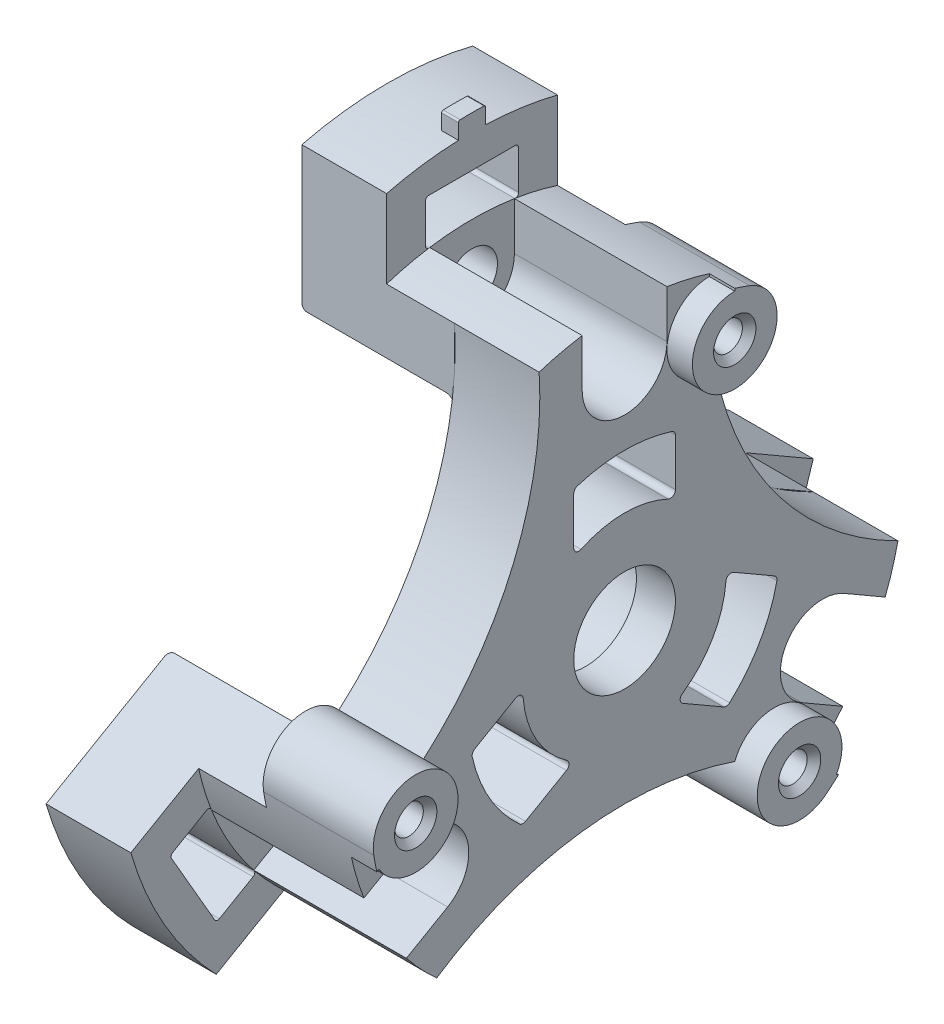
SolidWorks part; units mm, degrees
ref_plane "Front" through (0, 0, 0) normal (0, 0, 1) x (1, 0, 0)
ref_plane "Top" through (0, 0, 0) normal (0, 1, 0) x (1, 0, 0)
ref_plane "Right" through (0, 0, 0) normal (1, 0, 0) x (0, 0, -1)
sketch "草图1" plane through (0, 0, 0) normal (0, 0, 1) x (1, 0, 0)
  line L0 (-65.7429, 0) -> (89.5714, 0) construction
  line L1 (0, 67.1143) -> (0, -71.9143) construction
  line L2 (-7, 6) -> (-5, 6)
  line L3 (-5, 6) -> (-5, 16.5)
  line L4 (-5, 16.5) -> (0, 16.5)
  line L5 (0, 16.5) -> (0, 3)
  line L6 (-2.3, 3.975) -> (-7, 3.975)
  line L7 (-7, 3.975) -> (-7, 6)
  line L8 (-2.3, 3.975) -> (-2.3, 3)
  line L9 (-2.3, 3) -> (0, 3)
  dimension "D1" = 6
  dimension "D2" = 4.7
  dimension "D3" = 7.95
  dimension "D4" = 7
  dimension "D5" = 5
  dimension "D6" = 12
  dimension "D7" = 33
  dimension "D8" = 2.3
revolve "旋转1" add sketch "草图1" angle 360 about L0
sketch "草图2" plane through (-5, 0, 0) normal (-1, 0, 0) x (0, 0, 1)
  line L0 (-23.9515, 0) -> (26.381, 0) construction
  line L1 (0, 44.3891) -> (0, -20.5254) construction
  line L2 (0, 0) -> (-21.2641, -12.2768) construction
  line L3 (0, 0) -> (20.7932, -12.005) construction
  line L4 (0, 0) -> (-61.1055, 35.2793) construction
  line L5 (-5, 31.2128) -> (-5, 9) construction
  line L6 (5, 31.2128) -> (5, 9) construction
  circle A1 centre (-25, 14.4338) radius 20
  point P7 (0, 9)
  point P9 (-7.6795, 4.4338)
  dimension "D6" = 40
  dimension "D1" = 120
  dimension "D2" = 120
  dimension "D3" = 9
  dimension "D5" = 60
  dimension "D7" = 10
extrude "切除-拉伸1" cut sketch "草图2" against normal blind 10 contours A1
pattern_circular "阵列(圆周)1" count 3 over 360 about axis through (-7, 0, 0) along (-1, 0, 0) of "切除-拉伸1"
sketch "草图3" plane through (-5, 0, 0) normal (-1, 0, 0) x (0, 0, 1)
  line L0 (0, 18) -> (0, -12.9057) construction
  line L1 (-20.442, 0) -> (20.8303, 0) construction
  line L2 (-3, 8.4806) -> (-3, 5.6921)
  line L4 (3, 8.4806) -> (3, 5.6921)
  arc A0 (2.791, 8.7664) -> (-2.791, 8.7664) centre (0, 0) ccw
  circle A1 centre (0, 0) radius 6 construction
  arc A2 (2.5714, 5.421) -> (-2.5714, 5.421) centre (0, 0) ccw
  arc A3 (3, 5.6921) -> (2.5714, 5.421) centre (2.7, 5.6921) cw
  arc A4 (-2.5714, 5.421) -> (-3, 5.6921) centre (-2.7, 5.6921) cw
  arc A5 (3, 8.4806) -> (2.791, 8.7664) centre (2.7, 8.4806) ccw
  arc A6 (-2.791, 8.7664) -> (-3, 8.4806) centre (-2.7, 8.4806) ccw
  point P11 (3, 5.1962)
  point P16 (-3, 5.1962)
  point P19 (3, 8.6971)
  point P22 (-3, 8.6971)
  dimension "D1" = 9.2
  dimension "D3" = 0.3
  dimension "D2" = 6
extrude "切除-拉伸2" cut sketch "草图3" against normal blind 10
pattern_circular "阵列(圆周)2" count 3 over 360 about axis through (-2.3, 0, 0) along (-1, 0, 0) of "切除-拉伸2"
sketch "草图4" plane through (-5, 0, 0) normal (-1, 0, 0) x (0, 0, 1)
  line L0 (-16.7535, 0) -> (15.8993, 0) construction
  line L1 (0, 19.3876) -> (0, -16.6742) construction
  line L2 (-5.0408, 15.7111) -> (-5.0408, 11.9286)
  line L4 (5.0408, 11.9286) -> (5.0408, 15.7111)
  circle A0 centre (0, 0) radius 13.5 construction
  arc A1 (5.0408, 15.7111) -> (-5.0408, 15.7111) centre (0, 0) ccw construction
  arc A2 (5.0408, 15.7111) -> (-5.0408, 15.7111) centre (0, 0) ccw
  circle A3 centre (0, 13.5) radius 1.5
  arc A4 (-2.6744, 12.6708) -> (2.6744, 12.6708) centre (0, 13.5) ccw
  arc A5 (-2.6744, 12.6708) -> (-5.0408, 11.9286) centre (0, 0) ccw
  arc A6 (5.0408, 11.9286) -> (2.6744, 12.6708) centre (0, 0) ccw
  dimension "D1" = 27
  dimension "D2" = 3
  dimension "D4" = 5.6
  dimension "D5" = 25.9
extrude "凸台-拉伸1" add sketch "草图4" along normal blind 9
pattern_circular "阵列(圆周)3" count 3 over 360 about axis through (-65.7429, 0, 0) along (-1, 0, 0) of "凸台-拉伸1"
sketch "草图5" plane through (-14, 0, 0) normal (-1, 0, 0) x (0, 0, 1)
  line L0 (-16.1323, 0) -> (16.637, 0) construction
  line L1 (0, 17.8058) -> (0, -12.3621) construction
  line L3 (-2.8, 12.6437) -> (-2.8, 9.2908)
  line L4 (-2.8, 9.2908) -> (2.8, 9.2908)
  line L5 (2.8, 12.6437) -> (2.8, 9.2908)
  arc A2 (2.8, 12.6437) -> (-2.8, 12.6437) centre (0, 0) ccw
  point P10 (0, 9.2908)
  point P11 (0, 13.55)
  dimension "D1" = 5.6
  dimension "D2" = 25.9
extrude "切除-拉伸3" cut sketch "草图5" against normal blind 1.7 contours L4 L5 A2 L3
sketch "草图10" plane through (-5, 0, 0) normal (-1, 0, 0) x (0, 0, 1)
  point P1 (0, 0)
  dimension "D1" = 12.8775
pattern_circular "阵列(圆周)4" count 3 over 360 about axis through (-65.7429, 0, 0) along (-1, 0, 0) of "切除-拉伸3" reverse direction yes
sketch "草图6" plane through (0, 0, 0) normal (1, 0, 0) x (0, 0, -1)
  line L0 (-17.245, 0) -> (20.4566, 0) construction
  line L1 (0, 20.1005) -> (0, -14.3306) construction
  line L2 (-2.5, 16.3095) -> (-2.5, 13.5)
  line L3 (2.5, 16.3095) -> (2.5, 13.5)
  circle A0 centre (0, 0) radius 13.5 construction
  arc A1 (5.0408, 15.7111) -> (-5.0408, 15.7111) centre (0, 0) ccw construction
  arc A3 (2.5, 16.3095) -> (-2.5, 16.3095) centre (0, 0) ccw
  arc A4 (-2.5, 13.5) -> (2.5, 13.5) centre (0, 13.5) ccw
  dimension "D1" = 27
  dimension "D3" = 5
  dimension "D2" = 5
extrude "切除-拉伸4" cut sketch "草图6" against normal blind 9
pattern_circular "阵列(圆周)5" count 3 over 360 about axis through (-65.7429, 0, 0) along (-1, 0, 0) of "切除-拉伸4"
sketch "草图7" plane through (-5, 0, 0) normal (-1, 0, 0) x (0, 0, 1)
  line L0 (0, 19.1221) -> (0, -13.8647) construction
  line L1 (16.0973, 0) -> (-17.961, 0) construction
  line L2 (-5, 15.5767) -> (-5, 15.7242)
  arc A1 (-5.8929, 15.4118) -> (-5, 15.5767) centre (-5, 13.0767) ccw
  circle A5 centre (0, 0) radius 14 construction
  arc A6 (-2.5, 16.3095) -> (-5.0408, 15.7111) centre (0, 0) ccw construction
  arc A7 (-5, 15.7242) -> (-5.8929, 15.4118) centre (0, 0) ccw
  point P7 (-5, 13.0767)
  dimension "D1" = 28
  dimension "D3" = 5
  dimension "D2" = 5
extrude "凸台-拉伸2" add sketch "草图7" against normal blind 6.5
sketch "草图9" plane through (1.5, 0, 0) normal (1, 0, 0) x (0, 0, -1)
  line L0 (0, 17.5729) -> (0, -10.6538) construction
  line L1 (-14.0745, 0) -> (16.4041, 0) construction
  circle A0 centre (0, 0) radius 14 construction
  circle A1 centre (5, 13.0767) radius 0.85
  dimension "D1" = 1.7
extrude "切除-拉伸7" cut sketch "草图9" against normal blind 6.4 contours A1
chamfer "倒角3" distance 0.4 angle 45 1 edges at (1.5, 13.0767, -5.85)
pattern_circular "阵列(圆周)8" count 3 over 360 about axis through (-65.7429, 0, 0) along (-1, 0, 0) of "凸台-拉伸2", "切除-拉伸7", "倒角3"
chamfer "倒角4" distance 0.5 angle 60 1 edges at (-7, 0, 3.975) first distance on face at (-7, 0, 3.975)
fillet "圆角6" radius 0.5 9 edges at (-5, 12.3565, 3.8754) (-5, 12.3565, -3.8754) (-5, 10.7, 0) (-5, -2.822, -12.6388) (-5, -5.35, -9.2665) (-5, -9.5345, -8.7633) (-5, -9.5345, 8.7633) (-5, -2.822, 12.6388) (-5, -5.35, 9.2665)
fillet "圆角7" radius 0.5 1 edges at (-7, 0, 6)
sketch "草图11" plane through (-14, 0, 0) normal (-1, 0, 0) x (0, 0, 1)
  line L0 (-24.0343, 0) -> (27.0991, 0) construction
  line L1 (0, 23.8854) -> (0, -19.7008) construction
  line L2 (-5.0408, 15.7111) -> (-5.0408, 20.3345)
  line L3 (5.0408, 15.7111) -> (5.0408, 20.3345)
  line L4 (-2.55, 19) -> (2.55, 19)
  line L5 (-2.75, 18.8) -> (-2.75, 16.2692)
  line L7 (2.75, 18.8) -> (2.75, 16.2692)
  arc A0 (5.0408, 20.3345) -> (0, 20.95) centre (0, 0) ccw
  arc A1 (5.0408, 15.7111) -> (-5.0408, 15.7111) centre (0, 0) ccw construction
  arc A2 (5.0408, 15.7111) -> (2.75, 16.2692) centre (0, 0) ccw
  arc A3 (-2.75, 16.2692) -> (-5.0408, 15.7111) centre (0, 0) ccw
  arc A4 (0, 20.95) -> (-5.0408, 20.3345) centre (0, 0) ccw
  arc A5 (2.75, 18.8) -> (2.55, 19) centre (2.55, 18.8) ccw
  arc A6 (-2.75, 18.8) -> (-2.55, 19) centre (-2.55, 18.8) cw
  point P15 (0, 17)
  point P16 (0, 19)
  point P18 (2.75, 19)
  point P20 (0, 22)
  point P23 (-2.75, 19)
  dimension "D1" = 41.9
  dimension "D4" = 0.2
  dimension "D2" = 5.5
  dimension "D3" = 19
extrude "凸台-拉伸3" add sketch "草图11" against normal up to surface (5 mm away) up to face at (-9, 13.5, -1.5)
pattern_circular "阵列(圆周)9" count 3 over 360 about axis through (-6.134, 0, 0) along (-1, 0, 0) of "凸台-拉伸3"
sketch "草图12" plane through (-9, 0, 0) normal (1, 0, 0) x (0, 0, -1)
  line L0 (0, 23.0537) -> (0, -15.9342) construction
  line L1 (-23.5138, 0) -> (22.1093, 0) construction
  line L2 (-0.8, 21.8388) -> (-0.8, 20.9347)
  line L3 (0.8, 21.8388) -> (0.8, 20.9347)
  arc A0 (0.7032, 21.9387) -> (-0.7032, 21.9387) centre (0, 0) ccw
  arc A1 (5.0408, 20.3345) -> (-5.0408, 20.3345) centre (0, 0) ccw construction
  arc A2 (0.8, 20.9347) -> (-0.8, 20.9347) centre (0, 0) ccw
  arc A3 (-21.95, 0) -> (21.95, 0) centre (0, 0) ccw
  arc A4 (-0.8, 21.8388) -> (-0.7032, 21.9387) centre (-0.7, 21.8388) cw
  arc A5 (0.7032, 21.9387) -> (0.8, 21.8388) centre (0.7, 21.8388) cw
  dimension "D2" = 1
  dimension "D3" = 0.1
  dimension "D1" = 1.6
extrude "凸台-拉伸4" add sketch "草图12" against normal blind 1 contours A0 A4 L2 A2 L3 A5
pattern_circular "阵列(圆周)10" [suppressed] count 3 over 360 of bodies 124
fillet "圆角9" radius 0.3 6 edges at (-14, -9.0734, -9.2399) (-14, -3.4653, -12.4777) (-14, 12.5387, -3.2378) (-14, 12.5387, 3.2378) (-14, -9.0734, 9.2399) (-14, -3.4653, 12.4777)
fillet "圆角10" radius 0.2 6 edges at (-11.5, -10.5162, -12.7146) (-11.5, -5.753, -15.4646) (-11.5, -10.5162, 12.7146) (-11.5, -5.753, 15.4646) (-11.5, 16.2692, 2.75) (-11.5, 16.2692, -2.75)
sketch "草图14" plane through (0, 0, 0) normal (0, 0, 1) x (1, 0, 0)
  line L0 (6.5511, 0) -> (-13.5644, 0) construction
  line L1 (-11.2016, 4) -> (3.5999, 4) construction
  line L2 (-7.4213, 4.75) -> (-6.809, 4.75)
  line L3 (-6.809, 4.75) -> (-6.134, 4.075)
  line L4 (-6.134, 4.075) -> (-2.6377, 4.075)
  line L5 (-2.6377, 4.075) -> (-2.6377, 4)
  line L6 (-2.6377, 4) -> (-7.4213, 4)
  line L7 (-7.4213, 4) -> (-7.4213, 4.75)
  point P9 (-6.4776, 4.075)
  point P12 (-6.4804, 4.075)
  point P13 (-6.134, 4.075)
  dimension "D1" = 4
  dimension "D2" = 0.15
  dimension "D3" = 1.5
  dimension "D4" = 45
revolve "切除-旋转1" cut sketch "草图14" angle 360 about L1
pattern_circular "阵列(圆周)11" count 4 over 360 about axis through (-65.7429, 0, 0) along (-1, 0, 0) of "切除-旋转1"
